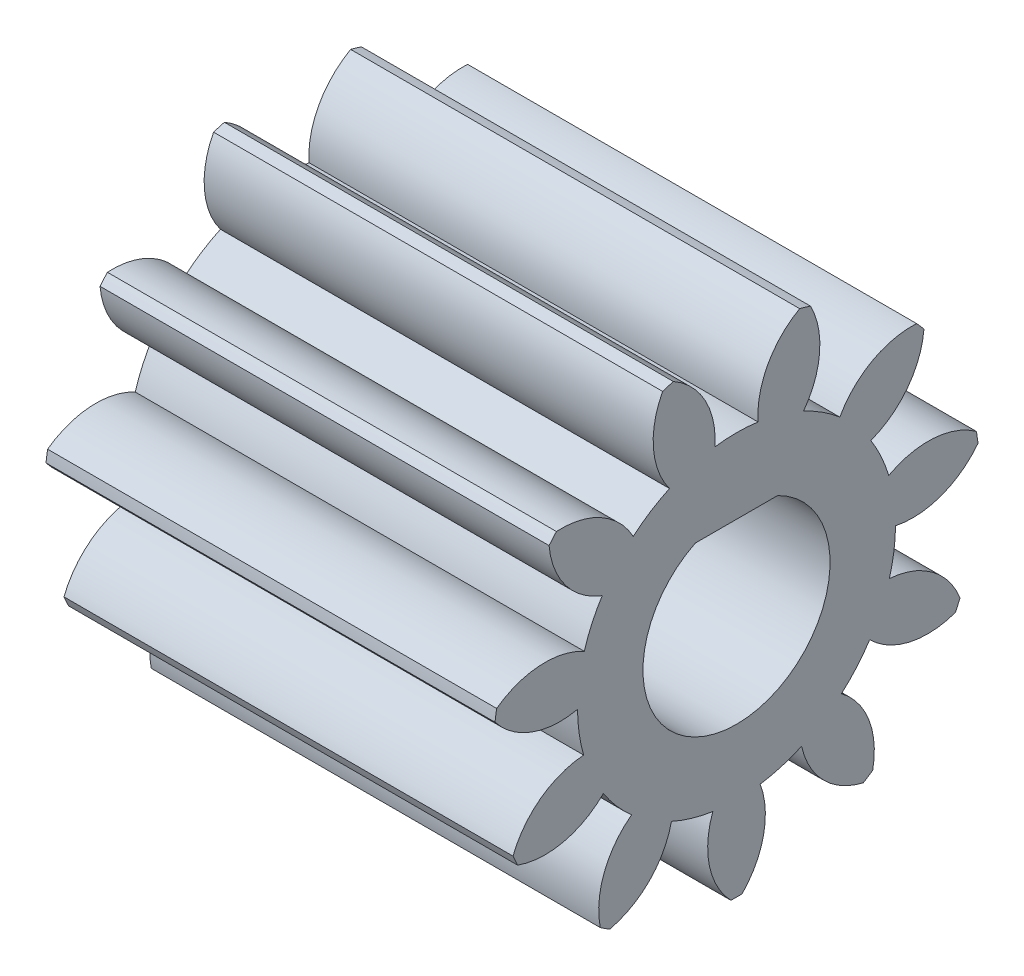
SolidWorks part; units mm, degrees
ref_plane "Plane1" through (0, 0, 0) normal (0, 0, 1) x (1, 0, 0)
ref_plane "Plane2" through (0, 0, 0) normal (0, 1, 0) x (1, 0, 0)
ref_plane "Plane3" through (0, 0, 0) normal (1, 0, 0) x (0, 0, -1)
sketch "HoldingSke" plane through (0, 0, 0) normal (0, 1, 0) x (1, 0, 0)
  line L0 (0, 0) -> (0.9816, -0.1908)
  line L1 (-15, 0) -> (100, 0) construction
  line L2 (0, 0) -> (-2.1039, 2.3779)
  line L3 (0, 0) -> (-11.863, 4.5341)
  line L4 (0, 0) -> (8.4773, 1.6478)
  line L5 (0, 0) -> (-46.8476, -17.4728)
  line L6 (0, 0) -> (-9.9476, -6.7116)
  line L7 (-2.1039, 2.3779) -> (8.6586, 51.2059)
  line L8 (-76.2, 54.61) -> (-75.3, 54.61)
  line L9 (-71.009, 38.7566) -> (-53.1078, 45.2721)
  line L10 (-76.2, 71.12) -> (104.1128, 71.12)
  line L11 (0, 0) -> (-12, 0)
  line L12 (-76.2, 101.6) -> (-76.162, 101.6)
  line L13 (24.9733, 27.94) -> (52.9518, 28.4284)
  line L14 (24.9733, 27.94) -> (24.9743, 27.94)
  line L15 (24.9733, 27.94) -> (100.4006, 29.5858)
  line L16 (-63.627, -1) -> (-12.827, -1)
  circle A0 centre (0, 0) radius 2.5
  circle A1 centre (0, 0) radius 4.249
  circle A2 centre (0, 0) radius 37.5
  circle A3 centre (0, 0) radius 2.5
  dimension "Num_teeth" = 11
  dimension "Pitch_radius" = 180.3128
  dimension "Width" = 12
  dimension "Thickness" = 12
sketch "BasProSke" plane through (0, 0, 0) normal (0, 1, 0) x (1, 0, 0)
  line L0 (-10, 0) -> (60, 0) construction
  line L1 (0, 0) -> (0, 6.5)
  line L2 (0, 0) -> (12, 0)
  line L3 (12, 0) -> (12, 6.5)
  line L4 (12, 6.5) -> (0, 6.5)
  dimension "Thickness" = 12
  dimension "Diameter" = 13
revolve "Base-Revolve" add sketch "BasProSke" angle 360 about L0
sketch "TooCutSke" plane through (0, 0, 0) normal (1, 0, 0) x (0, 0, -1)
  line L1 (0, 0) -> (0, 107) construction
  line L2 (0, 0) -> (-0.8491, 5.4341) construction
  line L3 (0, 0) -> (-3.0727, 10.4645) construction
  line L4 (-0.8491, 5.4341) -> (-1.5363, 5.2323) construction
  arc A0 (0.576, 4.2098) -> (-0.576, 4.2098) centre (0, 0) ccw
  arc A1 (1.7187, 6.295) -> (-1.7187, 6.295) centre (0, 0) ccw
  circle A2 centre (0, 0) radius 5.5 construction
  circle A3 centre (0, 0) radius 5.1683 construction
  arc A4 (-0.576, 4.2098) -> (-1.7187, 6.295) centre (-2.7707, 4.3629) ccw
  arc A5 (1.7187, 6.295) -> (0.576, 4.2098) centre (2.7707, 4.3629) ccw
extrude "ToothCut" cut sketch "TooCutSke" along normal through all
fillet "Breaks" [suppressed] radius 0.02 tangent propagation no
fillet "RootFillets" [suppressed] radius 0.251
pattern_circular "TeethCuts" count 11 every 32.727 about axis through (-10, 0, 0) along (1, 0, 0) of "ToothCut", "RootFillets", "Breaks"
sketch "HubNeaOneSke" plane through (0, 0, 0) normal (-1, 0, 0) x (0, 0, 1)
  circle A0 centre (0, 0) radius 4.249
  dimension "Diameter" = 8.498
extrude "HubNearOne" [suppressed] add sketch "HubNeaOneSke" along normal blind 38.0001
sketch "HubNeaBotSke" plane through (0, 0, 0) normal (-1, 0, 0) x (0, 0, 1)
  circle A0 centre (0, 0) radius 4.249
  dimension "Diameter" = 8.498
extrude "HubNearBoth" [suppressed] add sketch "HubNeaBotSke" along normal blind 19
ref_plane "FarPln" through (12, 0, 0) normal (1, 0, 0) x (0, 0, -1)
sketch "HubFarSke" plane through (12, 0, 0) normal (1, 0, 0) x (0, 0, -1)
  circle A0 centre (0, 0) radius 4.249
  dimension "Diameter" = 8.498
extrude "HubFar" [suppressed] add sketch "HubFarSke" along normal blind 19
sketch "BorSke" plane through (0, 0, 0) normal (1, 0, 0) x (0, 0, -1)
  circle A0 centre (0, 0) radius 2.5
  dimension "Diameter" = 5
extrude "Bore" cut sketch "BorSke" along normal mid plane 100.0001
sketch "KeySke" plane through (0, 0, 0) normal (1, 0, 0) x (0, 0, -1)
  line L0 (-1, 0) -> (-1, 3.4)
  line L1 (-1, 3.4) -> (1, 3.4)
  line L2 (1, 3.4) -> (1, 0)
  line L3 (0, 0) -> (0, 34) construction
  line L4 (-1, 0) -> (1, 0)
  dimension "Width" = 2
extrude "Keyway" [suppressed] cut sketch "KeySke" along normal mid plane 100.0001
pattern_circular "Keyway2" [suppressed] count 2 every 90 about axis through (-10, 0, 0) along (1, 0, 0) reverse direction yes
sketch "Sketch1" plane through (12, 0, 0) normal (1, 0, 0) x (0, 0, -1)
  line L0 (-1.1, 2.245) -> (1.1, 2.245)
  circle A0 centre (0, 0) radius 2.5 construction
  circle A2 centre (0, 0) radius 2.5
  arc A3 (1.1, 2.245) -> (-1.1, 2.245) centre (0, 0) ccw
  dimension "D1" = 0
extrude "Boss-Extrude1" add sketch "Sketch1" against normal blind 12
equation "' \"Module@HoldingSke\" = 6.35"
equation "' \"Num_teeth@HoldingSke\" = 12"
equation "' \"Ap@HoldingSke\" =  20"
equation "' \"Ap@HoldingSke\" = 20"
equation "' \"Width@HoldingSke\" = 0.5 * 25.4"
equation "' \"Hub_dia@HoldingSke\"= 1 * 25.4"
equation "' \"Hub_dia@HoldingSke\" = 1 * 25.4"
equation "' \"Overall_len@HoldingSke\" = 1.0 * 25.4"
equation "' \"Bore@HoldingSke\" = 0.75 * 25.4"
equation "' \"T_dim@HoldingSke\" = 0.1 * 25.4"
equation "' \"Width@KeySke\" = 0.25 * 25.4"
equation "' \"Show_teeth@HoldingSke\" = 13"
equation "' \"Backlash@HoldingSke\" = 0.009 * 25.4"
equation "' \"Addendum_fac@HoldingSke\" = 1.0"
equation "' \"Dedendum_fac@HoldingSke\" = 1.25"
equation "' \"Dedendum_add@HoldingSke\" = 0.00005 * 25.4"
equation "' \"Clearance_fac@HoldingSke\" = 0.25"
equation "\"Pitch@HoldingSke\" = 1 / \"Module@HoldingSke\""
equation "\"Overcut_dia@TooCutSke\" = (\"Num_teeth@HoldingSke\" + 2 * \"Addendum_fac@HoldingSke\") / \"Pitch@HoldingSke\" + 0.002 * 25.4"
equation "\"Pitch_dia@TooCutSke\" = \"Num_teeth@HoldingSke\" / \"Pitch@HoldingSke\""
equation "\"Base_dia@TooCutSke\" = \"Num_teeth@HoldingSke\" / \"Pitch@HoldingSke\" * cos((\"Ap@HoldingSke\"  * 3.14159265 / 180))"
equation "\"Root_dia@TooCutSke\" = (\"Num_teeth@HoldingSke\" + 2) / \"Pitch@HoldingSke\" - 2 * (\"Addendum_fac@HoldingSke\" + \"Dedendum_fac@HoldingSke\") / \"Pitch@HoldingSke\" - \"Dedendum_add@HoldingSke\" * 2"
equation "\"Half_ang@TooCutSke\" = 180 / \"Num_teeth@HoldingSke\""
equation "\"Half_CT@TooCutSke\" = \"Num_teeth@HoldingSke\" / \"Pitch@HoldingSke\" * sin((3.14159265 / 2 / \"Num_teeth@HoldingSke\")) / 2 - 7 * \"Backlash@HoldingSke\" / 4"
equation "\"Flank_rad@TooCutSke\" = \"Num_teeth@HoldingSke\" / \"Pitch@HoldingSke\" / 5"
equation "\"Radius@RootFillets\" = \"Clearance_fac@HoldingSke\" / \"Pitch@HoldingSke\" + \"Dedendum_add@HoldingSke\""
equation "\"Break_rad@Breaks\" = 0.02 / \"Pitch@HoldingSke\""
equation "\"Thickness@HoldingSke\" = \"Width@HoldingSke\""
equation "\"OAL@HoldingSke\" = \"Thickness@HoldingSke\""
equation "\"MHD@HoldingSke\" = (\"Num_teeth@HoldingSke\" + 2) / \"Pitch@HoldingSke\" - 2 * (\"Addendum_fac@HoldingSke\" + \"Dedendum_fac@HoldingSke\")  / \"Pitch@HoldingSke\" - \"Dedendum_add@HoldingSke\" * 2"
equation "\"MBD@HoldingSke\" = (\"Num_teeth@HoldingSke\" + 2) / \"Pitch@HoldingSke\" - 2 * (\"Addendum_fac@HoldingSke\" + \"Dedendum_fac@HoldingSke\")  / \"Pitch@HoldingSke\" - \"Dedendum_add@HoldingSke\" * 2 - 0.002 * 25.4"
equation "\"MHD@HoldingSke\" = ((sgn( \"MHD@HoldingSke\" - \"Hub_dia@HoldingSke\" )-1)*( \"MHD@HoldingSke\" - \"Hub_dia@HoldingSke\" ))/-2+ \"Hub_dia@HoldingSke\""
equation "\"MBD@HoldingSke\" = ((sgn( \"MBD@HoldingSke\" - \"Bore@HoldingSke\" )-1)*( \"MBD@HoldingSke\" - \"Bore@HoldingSke\" ))/-2+ \"Bore@HoldingSke\""
equation "\"OAL@HoldingSke\" = ((sgn( \"OAL@HoldingSke\" - \"Overall_len@HoldingSke\" )+1)*( \"OAL@HoldingSke\" - \"Overall_len@HoldingSke\" ))/2 + \"Overall_len@HoldingSke\" + 0.000002 * 25.4"
equation "\"Num_teeth@TeethCuts\" = int( \"Show_teeth@HoldingSke\" ) + 1"
equation "\"Num_teeth@TeethCuts\" = ((sgn( \"Num_teeth@TeethCuts\" - \"Num_teeth@HoldingSke\" )-1)*( \"Num_teeth@TeethCuts\" - \"Num_teeth@HoldingSke\" ))/-2+ \"Num_teeth@HoldingSke\""
equation "\"Num_teeth@TeethCuts\" = ((sgn( \"Num_teeth@TeethCuts\" - 2.0)+1)*( \"Num_teeth@TeethCuts\" - 2.0))/2 +2.0"
equation "\"Angle@TeethCuts\" = 360.0 / \"Num_teeth@HoldingSke\""
equation "\"Diameter@BasProSke\" = (\"Num_teeth@HoldingSke\" + 2 * \"Addendum_fac@HoldingSke\") / \"Pitch@HoldingSke\""
equation "\"Thickness@BasProSke\"  = \"Thickness@HoldingSke\""
equation "' \"Fillet_rad@BasProSke\" =  \"Thickness@HoldingSke\" * 0.05"
equation "' \"Fillet_rad@BasProSke\" = \"Thickness@HoldingSke\" * 0.05"
equation "\"MHD@HoldingSke\" = ((sgn( \"MHD@HoldingSke\" - \"Root_dia@TooCutSke\" )-1)*( \"MHD@HoldingSke\" - \"Root_dia@TooCutSke\" ))/-2+ \"Root_dia@TooCutSke\""
equation "\"Diameter@HubNeaOneSke\" = \"MHD@HoldingSke\""
equation "\"Length@HubNearOne\" = \"OAL@HoldingSke\" - \"Thickness@BasProSke\""
equation "\"Diameter@HubNeaBotSke\" = \"MHD@HoldingSke\""
equation "\"Length@HubNearBoth\" = ( \"OAL@HoldingSke\" - \"Thickness@BasProSke\" ) / 2.0"
equation "\"Thickness@FarPln\" = \"Thickness@BasProSke\""
equation "\"Diameter@HubFarSke\" = \"MHD@HoldingSke\""
equation "\"Length@HubFar\" = ( \"OAL@HoldingSke\" - \"Thickness@BasProSke\" ) / 2.0"
equation "\"Diameter@BorSke\" = \"MBD@HoldingSke\""
equation "\"D1@Bore\" = \"OAL@HoldingSke\" * 2.0"
equation "\"D1@Keyway\" = \"OAL@HoldingSke\" * 2.0"
equation "\"Offset@KeySke\" = \"T_dim@HoldingSke\" + \"MBD@HoldingSke\" / 2.0"
